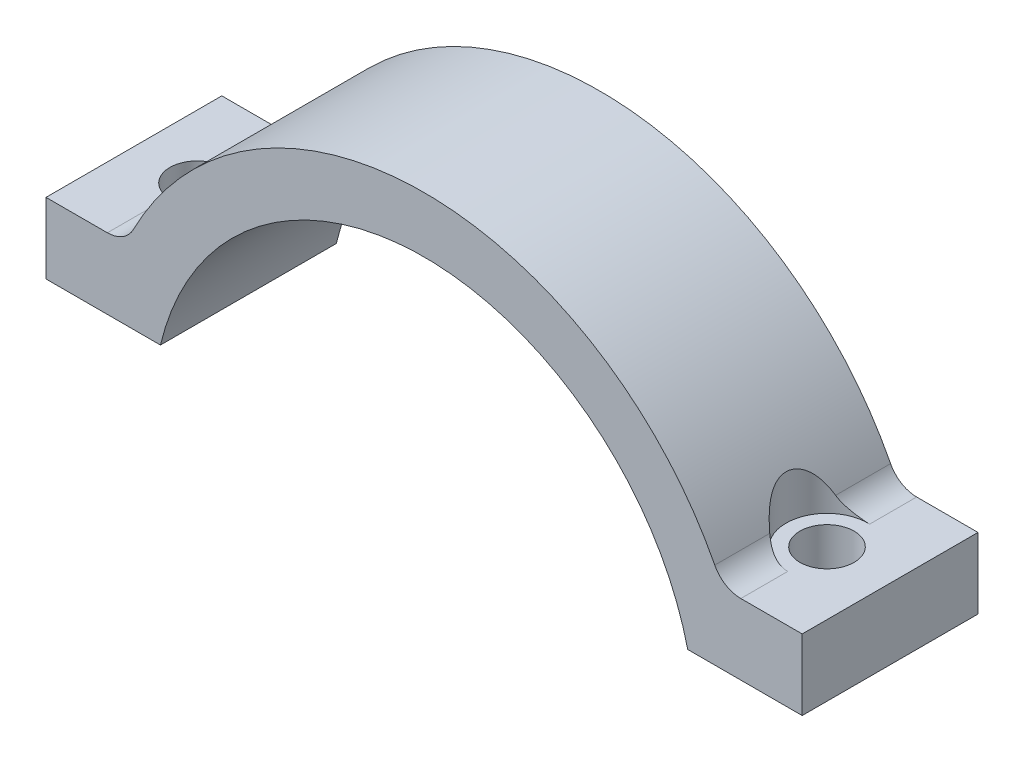
SolidWorks part; units mm, degrees
material "2024 Alloy"
ref_plane "Front Plane" through (0, 0, 0) normal (0, 0, 1) x (1, 0, 0)
ref_plane "Top Plane" through (0, 0, 0) normal (0, 1, 0) x (1, 0, 0)
ref_plane "Right Plane" through (0, 0, 0) normal (1, 0, 0) x (0, 0, -1)
sketch "Sketch1" plane through (0, 0, 0) normal (0, 0, 1) x (1, 0, 0)
  line L0 (0, 0) -> (0, -4.2926) construction
  line L1 (0, 0) -> (0, 14.2074) construction
  line L2 (-25.8064, 0) -> (25.8064, 0) construction
  line L3 (25.8064, 0) -> (25.8064, 4.826)
  line L4 (25.8064, 4.826) -> (20.3614, 4.826)
  line L5 (-25.8064, 4.826) -> (-25.8064, 0)
  line L6 (-25.8064, 0) -> (-17.9951, 0)
  line L7 (25.8064, 0) -> (17.9951, 0)
  line L8 (-20.3614, 4.826) -> (-25.8064, 4.826)
  arc A0 (17.9951, 0) -> (-17.9951, 0) centre (0, -4.2926) ccw
  arc A1 (20.3614, 4.826) -> (-20.3614, 4.826) centre (0, -4.2926) ccw
  point P8 (0, 0)
  dimension "D3" = 3.81
  dimension "D1" = 4.2926
  dimension "D2" = 18.5
  dimension "D4" = 51.6128
  dimension "D5" = 4.826
extrude "Boss-Extrude1" add sketch "Sketch1" along normal blind 6 and the other way blind 6
fillet "Fillet1" radius 2 2 edges at (20.3614, 4.826, 0) (-20.3614, 4.826, 0)
sketch "Sketch3" plane through (0, 0, 0) normal (0, 1, 0) x (1, 0, 0)
  line L0 (0, 0) -> (21.5, 0) construction
  line L1 (0, 0) -> (0, 7.8194) construction
  circle A0 centre (21.5, 0) radius 1.85
  circle A1 centre (-21.5, 0) radius 1.85
  dimension "D2" = 3.7
  dimension "D1" = 21.5
extrude "Cut-Extrude2" cut sketch "Sketch3" against normal blind 4.826 and the other way blind 4.826
sketch "Sketch4" plane through (0, 4.826, 0) normal (0, 1, 0) x (1, 0, 0)
  line L0 (0, 0) -> (0, 11.0003) construction
  circle A0 centre (-21.5, 0) radius 2.794
  circle A1 centre (21.5, 0) radius 2.794
  dimension "D1" = 5.588
extrude "Cut-Extrude3" cut sketch "Sketch4" along normal blind 4.826
